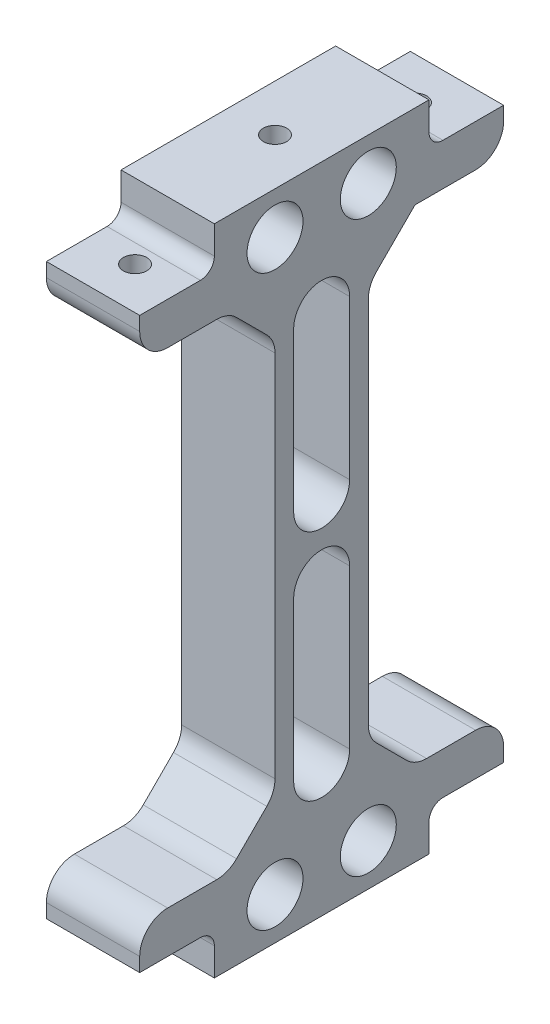
SolidWorks part; units mm, degrees
material "7050-T73510"
ref_plane "Front Plane" through (0, 0, 0) normal (0, 0, 1) x (1, 0, 0)
ref_plane "Top Plane" through (0, 0, 0) normal (0, 1, 0) x (1, 0, 0)
ref_plane "Right Plane" through (0, 0, 0) normal (1, 0, 0) x (0, 0, -1)
sketch "Sketch1" plane through (0, 0, 0) normal (1, 0, 0) x (0, 0, -1)
  line L0 (-10, 4.5) -> (0, 4.5)
  line L1 (-10, -4.5) -> (0, -4.5)
  line L2 (0, 4.5) -> (0, 56.5)
  line L3 (0, 30.5) -> (-10, 30.5)
  line L4 (-10, 56.5) -> (-10, 4.5)
  line L5 (0, 30.5) -> (-21.5774, 30.5) construction
  line L6 (-10, 65.5) -> (0, 65.5)
  line L7 (-10, 56.5) -> (0, 56.5)
  line L8 (-5, 65.5) -> (-5, -4.5) construction
  line L9 (-5, 51.5) -> (-5, 34.5) construction
  line L10 (-2, 51.5) -> (-2, 34.5)
  line L11 (-8, 51.5) -> (-8, 34.5)
  line L12 (-5, 26.5) -> (-5, 9.5) construction
  line L13 (-2, 26.5) -> (-2, 9.5)
  line L14 (-8, 26.5) -> (-8, 9.5)
  line L15 (0, 4.5) -> (10, 4.5)
  line L16 (10, 4.5) -> (10, -4.5)
  line L17 (10, -4.5) -> (0, -4.5)
  line L18 (-10, 4.5) -> (-20, 4.5)
  line L19 (-20, -4.5) -> (-10, -4.5)
  line L20 (10, 65.5) -> (0, 65.5)
  line L21 (0, 56.5) -> (10, 56.5)
  line L22 (-10, 56.5) -> (-20, 56.5)
  line L23 (-20, 65.5) -> (-10, 65.5)
  line L24 (-24.5, 61) -> (-24.5, 65.5)
  line L25 (-24.5, 65.5) -> (-20, 65.5)
  line L26 (-24.5, 61) -> (-24.5, 56.5)
  line L27 (-24.5, 56.5) -> (-20, 56.5)
  line L28 (14.5, 56.5) -> (10, 56.5)
  line L29 (14.5, 61) -> (14.5, 56.5)
  line L30 (14.5, 61) -> (14.5, 65.5)
  line L31 (14.5, 65.5) -> (10, 65.5)
  line L32 (-20, 4.5) -> (-24.5, 4.5)
  line L33 (-24.5, 4.5) -> (-24.5, 0)
  line L34 (-24.5, 0) -> (-24.5, -4.5)
  line L35 (-24.5, -4.5) -> (-20, -4.5)
  line L36 (10, 4.5) -> (14.5, 4.5)
  line L37 (14.5, 4.5) -> (14.5, 0)
  line L38 (14.5, 0) -> (14.5, -4.5)
  line L39 (14.5, -4.5) -> (10, -4.5)
  circle A0 centre (0, 0) radius 4.5
  circle A1 centre (-10, 0) radius 4.5
  circle A2 centre (-10, 0) radius 3
  circle A3 centre (0, 0) radius 3
  circle A4 centre (0, 61) radius 3
  circle A5 centre (-10, 61) radius 3
  circle A6 centre (-10, 61) radius 4.5
  circle A7 centre (0, 61) radius 4.5
  arc A8 (-2, 51.5) -> (-8, 51.5) centre (-5, 51.5) ccw
  arc A9 (-8, 34.5) -> (-2, 34.5) centre (-5, 34.5) ccw
  arc A10 (-2, 26.5) -> (-8, 26.5) centre (-5, 26.5) ccw
  arc A11 (-8, 9.5) -> (-2, 9.5) centre (-5, 9.5) ccw
  circle A12 centre (10, 0) radius 4.5
  circle A13 centre (-20, 0) radius 4.5
  circle A14 centre (10, 61) radius 4.5
  circle A15 centre (-20, 61) radius 4.5
  point P28 (-5, 43)
  point P33 (-5, 18)
  dimension "D1" = 9
  dimension "D3" = 6
  dimension "D4" = 6
  dimension "D7" = 3
  dimension "D8" = 3
  dimension "D5" = 10
  dimension "D6" = 61
  dimension "D9" = 17
  dimension "D10" = 17
  dimension "D11" = 4
  dimension "D12" = 4
  dimension "D13" = 10
extrude "Boss-Extrude1" add sketch "Sketch1" along normal blind 10 contours A6 A15 | A5 A15 A6 | A15 L22 A6 | A15 A6 L23 | A7 A14 L20 | A14 A7 | L21 A14 A7 | A14 A7 A4 | A7 A14 A4 | L7 A7 L6 A6 | A15 A5 A6 | L7 L4 L3 L2 A9 L11 A8 L10 | L3 L4 L0 L2 A11 L14 A10 L13 | A1 L1 A0 L0 | A12 A0 A3 | A2 A13 A1 | L18 A13 A1 | A13 A1 | A13 A2 A1 | A1 A13 L19 | A12 A0 L17 | L16 A12 A0 | A0 A12 A3 | A12 L15 A0 | L16 A12 | A15 L25 L24 | A15 L26 L27 | L29 A14 L28 | L31 A14 L30 | L35 A13 L34 | L33 A13 L32 | A12 L37 L36 | A12 L39 L38 region at (0, 17.5, 9.7214) region at (0, 0, 15) region at (0, 0, 5) region at (0, 3.092, 6.908) region at (0, 0, -5) region at (0, 3.092, -3.092) region at (0, 43.5, 9.7214) region at (0, 3.4948, 23.4948) region at (0, 0, 20) region at (0, 0, -11.9099) region at (0, 3.4948, -13.4948) region at (0, 0, -8.0901) region at (0, 61, 5) region at (0, 61, 15) region at (0, 61, 14.3727) region at (0, -3.4948, 23.4948) region at (0, 61, -5) region at (0, 61, 4.3727) region at (0, -3.4948, -13.4948) region at (0, 57.5052, 23.4948) region at (0, 61, 20) region at (0, 57.5052, -13.4948) region at (0, 61, -10) region at (0, 64.4948, 23.4948) region at (0, 64.4948, -13.4948)
chamfer "Chamfer1" distance 5 angle 45 4 edges at (5, 56.5, 10) (5, 56.5, 0) (5, 4.5, 0) (5, 4.5, 10)
fillet "Fillet1" radius 3 15 edges at (5, 51.5, 0) (5, 9.5, 0) (5, 9.5, 10) (5, 51.5, 10) (5, 56.5, 15) (5, 56.5, 24.5) (5, 65.5, 24.5) (5, 65.5, -14.5) (5, 56.5, -14.5) (5, 4.5, -5) (5, 4.5, -14.5) (5, -4.5, -14.5) (5, -4.5, 24.5) (5, 4.5, 24.5) (5, 4.5, 15)
sketch "Sketch4" plane through (10, 0, 0) normal (1, 0, 0) x (0, 0, -1)
  line L0 (-16.5, 65.5) -> (-16.5, 61)
  line L1 (-21.5, 65.5) -> (11.5, 65.5) construction
  line L2 (-16.5, 61) -> (-24.5, 61)
  line L3 (-24.5, 59.5) -> (-24.5, 62.5) construction
  line L4 (-24.5, 61) -> (-24.5, 65.5)
  line L5 (-24.5, 65.5) -> (-16.5, 65.5)
  line L6 (-5, 65.5) -> (-5, 54.5) construction
  line L7 (-10, 30.5) -> (0, 30.5) construction
  line L8 (-10, 50.2574) -> (-10, 10.7426) construction
  line L9 (0, 10.7426) -> (0, 50.2574) construction
  line L10 (14.5, 65.5) -> (6.5, 65.5)
  line L11 (14.5, 61) -> (14.5, 65.5)
  line L12 (6.5, 61) -> (14.5, 61)
  line L13 (6.5, 65.5) -> (6.5, 61)
  line L14 (6.5, -4.5) -> (6.5, 0)
  line L15 (6.5, 0) -> (14.5, 0)
  line L16 (14.5, 0) -> (14.5, -4.5)
  line L17 (14.5, -4.5) -> (6.5, -4.5)
  line L18 (-24.5, -4.5) -> (-16.5, -4.5)
  line L19 (-24.5, 0) -> (-24.5, -4.5)
  line L20 (-16.5, 0) -> (-24.5, 0)
  line L21 (-16.5, -4.5) -> (-16.5, 0)
  arc A0 (-2, 51.5) -> (-8, 51.5) centre (-5, 51.5) ccw construction
  dimension "D1" = 8
  dimension "D2" = 4.5
extrude "Cut-Extrude1" cut sketch "Sketch4" against normal blind 10
fillet "Fillet2" radius 1.5 4 edges at (5, 0, 16.5) (5, 0, -6.5) (5, 61, -6.5) (5, 61, 16.5)
hole_wizard "M3 Tapped Hole1" positions "Sketch6" profile "Sketch5" tap size "M3" standard "ISO"
sketch "Sketch6" plane through (0, 61, 0) normal (0, 1, 0) x (1, 0, 0)
  line L3 (10, -24.5) -> (10, -18) construction
  line L4 (0, -16.5) -> (10, -16.5) construction
  line L5 (0, 6.5) -> (10, 6.5) construction
  point P0 (5, -20)
  point P2 (5, 10)
  dimension "D1" = 5
  dimension "D2" = 3.5
  dimension "D3" = 3.5
sketch "Sketch5" plane through (5, 61, 20) normal (1, 0, 0) x (0, 0, 1)
  line L0 (0, 0) -> (0, 18.2511)
  line L1 (0, 18.2511) -> (1.25, 17.5)
  line L2 (1.25, 17.5) -> (1.25, 0)
  line L5 (1.25, 0) -> (0, 0)
  line L10 (0, 18.2511) -> (-1.25, 17.5) construction
  line L11 (0, -6.35) -> (0, 107.95) construction
  dimension "Tap Drill Dia." = 2.5
  dimension "Tap Drill Depth" = 17.5
  dimension "Drill Angle" = 118
cosmetic thread "Hole Thread1" parameters "D1"=4.5, "D2"=3
cosmetic thread "Hole Thread2" parameters "D1"=4.5, "D2"=3
hole_wizard "M3 Tapped Hole2" positions "Sketch8" profile "Sketch7" tap size "M3" standard "ISO"
sketch "Sketch8" plane through (0, 65.5, 0) normal (0, 1, 0) x (1, 0, 0)
  line L0 (0, -16.5) -> (10, -16.5) construction
  line L1 (5, -16.5) -> (5, 6.5) construction
  line L2 (0, 6.5) -> (10, 6.5) construction
  point P0 (5, -5)
sketch "Sketch7" plane through (5, 65.5, 5) normal (1, 0, 0) x (0, 0, 1)
  line L0 (0, 0) -> (0, 8.2511)
  line L1 (0, 8.2511) -> (1.25, 7.5)
  line L2 (1.25, 7.5) -> (1.25, 0)
  line L5 (1.25, 0) -> (0, 0)
  line L10 (0, 8.2511) -> (-1.25, 7.5) construction
  line L11 (0, -6.35) -> (0, 107.95) construction
  dimension "Tap Drill Dia." = 2.5
  dimension "Tap Drill Depth" = 7.5
  dimension "Drill Angle" = 118
cosmetic thread "Hole Thread3"
